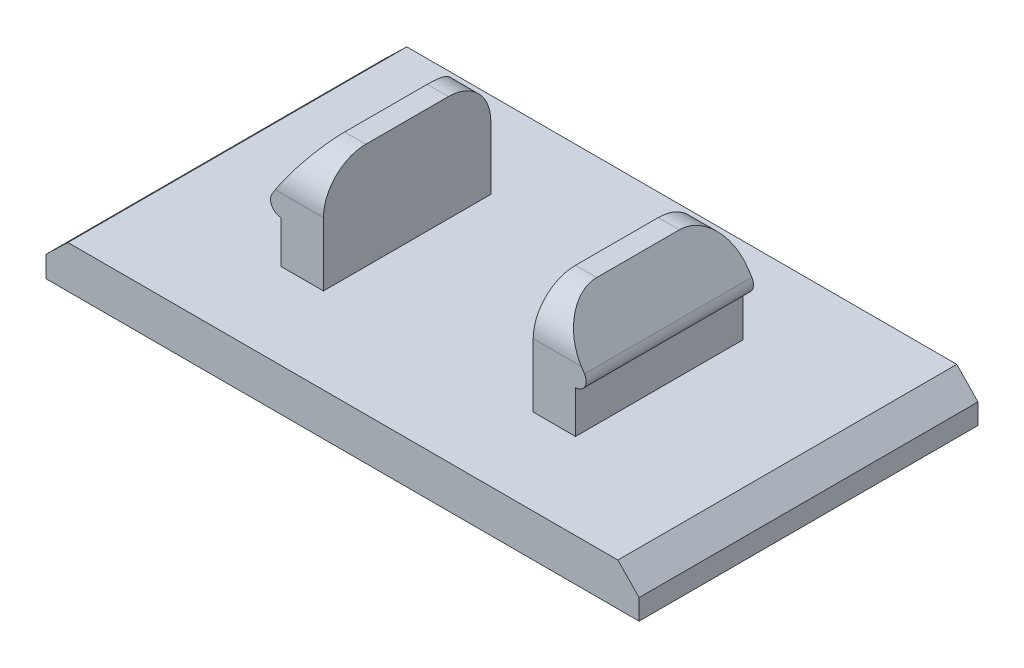
SolidWorks part; units mm, degrees
note: The reader was unsure of these and kept them because the rebuilt part matched: shared geometry of "Sketch1<3>", "Sketch2<3>".
ref_plane "Front Plane" through (0, 0, 0) normal (0, 0, 1) x (1, 0, 0)
ref_plane "Top Plane" through (0, 0, 0) normal (0, 1, 0) x (1, 0, 0)
ref_plane "Right Plane" through (0, 0, 0) normal (1, 0, 0) x (0, 0, -1)
sketch "Sketch1" plane through (0, 0, 0) normal (0, 1, 0) x (1, 0, 0)
  line L0 (-4.95, 3.95) -> (-4.95, -3.95)
  line L1 (-14, 8) -> (14, 8)
  line L2 (-14, 8) -> (-14, -8)
  line L3 (-14, -8) -> (14, -8)
  line L4 (14, 8) -> (14, -8)
  line L5 (-14, 8) -> (14, -8) construction
  line L6 (-14, -8) -> (14, 8) construction
  line L7 (-6.95, 3.95) -> (6.95, 3.95)
  line L8 (-6.95, 3.95) -> (-6.95, -3.95)
  line L9 (-6.95, -3.95) -> (6.95, -3.95)
  line L10 (6.95, 3.95) -> (6.95, -3.95)
  line L11 (-6.95, 3.95) -> (6.95, -3.95) construction
  line L12 (-6.95, -3.95) -> (6.95, 3.95) construction
  line L13 (4.95, 3.95) -> (4.95, -3.95)
  point P0 (0, 0)
  point P5 (0, 0)
  point P15 (-4.95, 0)
  dimension "D1" = 16
  dimension "D2" = 28
  dimension "D3" = 7.9
  dimension "D4" = 13.9
  dimension "D5" = 2
  dimension "D6" = 2
extrude "Boss-Extrude1" add sketch "Sketch1" along normal blind 2 contours L3 L4 L1 L2
chamfer "Chamfer1" distance 1 angle 46 2 edges at (14, 2, 0) (-14, 2, 0)
extrude "Boss-Extrude2" add sketch "Sketch1<3>" along normal blind 7 contours L8 L9 L0 L7 | L7 L13 L9 L10
sketch "Sketch1<3>" plane through (0, 0, 0) normal (0, 1, 0) x (1, 0, 0) same geometry as "Sketch1"
sketch "Sketch2" plane through (0, 0, 3.95) normal (0, 0, 1) x (1, 0, 0)
  line L0 (-6.95, 7) -> (-6.95, 2) construction
  line L2 (-12.9645, 2) -> (13, 2) construction
  line L3 (-7.3717, 4.7687) -> (-5.95, 7)
  line L4 (-6.95, 7) -> (-4.95, 7) construction
  line L5 (-5.95, 7) -> (-5.95, 4.5)
  line L6 (-5.95, 4.5) -> (-6.45, 4.5)
  line L7 (-5.95, 7) -> (-7.45, 7)
  line L8 (-7.45, 7) -> (-7.45, 4.5)
  line L9 (0, 0) -> (0, 7.3988) construction
  line L10 (7.45, 7) -> (7.45, 4.5)
  line L11 (5.95, 7) -> (7.45, 7)
  line L12 (5.95, 4.5) -> (6.45, 4.5)
  line L13 (5.95, 7) -> (5.95, 4.5)
  line L14 (7.3717, 4.7687) -> (5.95, 7)
  circle A0 centre (-6.95, 4.5) radius 0.5
  circle A2 centre (6.95, 4.5) radius 0.5
  line M5 (-4.95, 7) -> (-6.95, 7)
  line M6 (-6.95, 7) -> (-6.95, 2)
  dimension "D1" = 1
  dimension "D3" = 2.5
extrude "Cut-Extrude1" cut sketch "Sketch2" against normal through all contours L3 M6 M5 | L14 A2 L10 L11
extrude "Boss-Extrude3" add sketch "Sketch2<3>" against normal up to surface (7.9 mm away) contours A0 M6 | A0 L3 M6 | A2 | L12 A2 L14 L13 up to face at (-5.95, 4.6861, -3.95)
sketch "Sketch2<3>" plane through (0, 0, 3.95) normal (0, 0, 1) x (1, 0, 0) same geometry as "Sketch2"
fillet "Fillet1" radius 2 4 edges at (5.45, 7, -3.95) (5.45, 7, 3.95) (-5.45, 7, -3.95) (-5.45, 7, 3.95)
